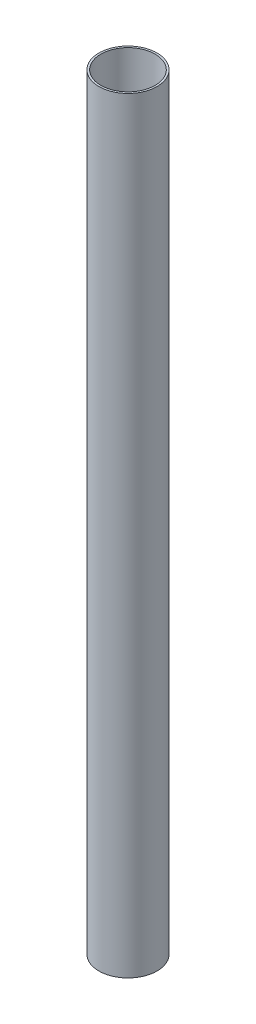
SolidWorks part; units mm, degrees
material "E-Glass Fiber"
ref_plane "Front Plane" through (0, 0, 0) normal (0, 0, 1) x (1, 0, 0)
ref_plane "Top Plane" through (0, 0, 0) normal (0, 1, 0) x (1, 0, 0)
ref_plane "Right Plane" through (0, 0, 0) normal (1, 0, 0) x (0, 0, -1)
sketch "Sketch1" plane through (0, 0, 0) normal (0, 0, 1) x (1, 0, 0)
  line L0 (0, 0) -> (0, -40.98) construction
  line L1 (28.9179, 18.1612) -> (28.9179, -743.8388) construction
  line L2 (26.9875, 18.1612) -> (28.9179, 18.1612)
  line L3 (26.9875, 18.1612) -> (26.9875, -743.8388)
  line L4 (26.9875, -743.8388) -> (28.9179, -743.8388)
  line L5 (28.9179, 18.1612) -> (28.9179, -743.8388)
revolve "Revolve1" add sketch "Sketch1" angle 360 about L0
